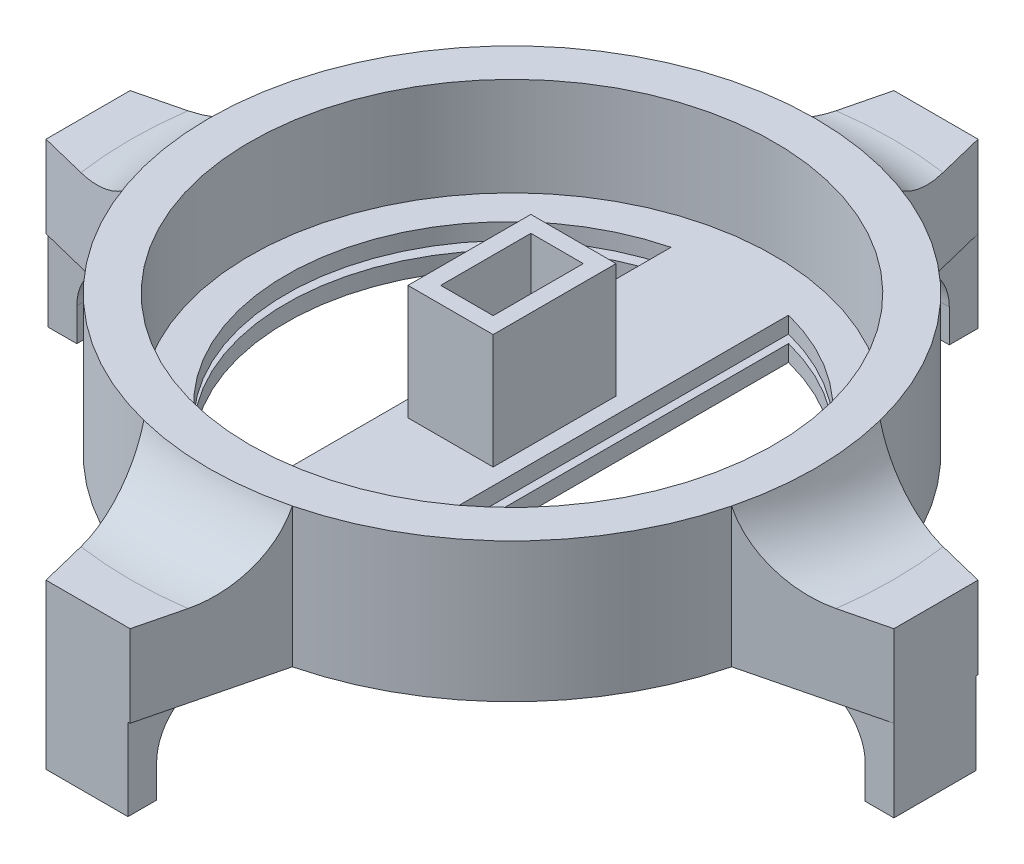
SolidWorks part; units mm, degrees
ref_plane "Front Plane" through (0, 0, 0) normal (0, 0, 1) x (1, 0, 0)
ref_plane "Top Plane" through (0, 0, 0) normal (0, 1, 0) x (1, 0, 0)
ref_plane "Right Plane" through (0, 0, 0) normal (1, 0, 0) x (0, 0, -1)
sketch "Sketch4" plane through (0, 0, 0) normal (0, 1, 0) x (1, 0, 0)
  line L0 (0, -46.7905) -> (24.3942, -46.7905) construction
  line L1 (0, -46.7905) -> (0, -24.9936) construction
  circle A0 centre (0, -46.7905) radius 17
  dimension "D1" = 34
extrude "Boss-Extrude3" add sketch "Sketch4" along normal blind 6 separate body
shell "Shell4" thickness 0.5 removed face at (0, 6, 63.7905) outward yes
ref_plane "Plane2" through (0, 0, 0) normal (0, 1, 0) x (1, 0, 0)
sketch "Sketch5" plane through (0, 0, 0) normal (0, 1, 0) x (1, 0, 0)
  line L0 (17, -46.7905) -> (-25.0436, -46.7905) construction
  line L1 (1.6, -44.0405) -> (-1.6, -44.0405)
  line L2 (1.6, -44.0405) -> (1.6, -49.5405)
  line L3 (1.6, -49.5405) -> (-1.6, -49.5405)
  line L4 (-1.6, -44.0405) -> (-1.6, -49.5405)
  line L5 (0, -29.7905) -> (0, -85.3723) construction
  circle A0 centre (0, -46.7905) radius 17 construction
  circle A1 centre (0, -46.7905) radius 17 construction
  dimension "D1" = 5.5
  dimension "D2" = 3.2
  dimension "D3" = 2.75
  dimension "D4" = 1.6
extrude "Boss-Extrude4" add sketch "Sketch5" along normal blind 8
shell "Shell5" thickness 1 removed face at (0, 8, 46.7905) outward yes
sketch "Sketch6" plane through (0, 0, 0) normal (0, 1, 0) x (1, 0, 0)
  line L1 (-2.5652, -72.6598) -> (2.5652, -72.6598)
  line L2 (2.5652, -72.6598) -> (4.5312, -64.727)
  line L3 (-2.5652, -72.6598) -> (-4.5312, -64.727)
  line L4 (-25.8693, -44.2252) -> (-17.9365, -42.2592)
  line L5 (-25.8693, -49.3557) -> (-17.9365, -51.3217)
  line L6 (-25.8693, -44.2252) -> (-25.8693, -49.3557)
  line L7 (2.5652, -20.9211) -> (4.5312, -28.854)
  line L8 (-2.5652, -20.9211) -> (-4.5312, -28.854)
  line L9 (2.5652, -20.9211) -> (-2.5652, -20.9211)
  line L10 (25.8693, -49.3557) -> (17.9365, -51.3217)
  line L11 (25.8693, -44.2252) -> (17.9365, -42.2592)
  line L12 (25.8693, -49.3557) -> (25.8693, -44.2252)
  circle A0 centre (0, -46.7905) radius 18.5 construction
  arc A1 (4.5312, -64.727) -> (-4.5312, -64.727) centre (0, -46.7905) cw
  arc A2 (-17.9365, -51.3217) -> (-17.9365, -42.2592) centre (0, -46.7905) cw
  arc A3 (-4.5312, -28.854) -> (4.5312, -28.854) centre (0, -46.7905) cw
  arc A4 (17.9365, -42.2592) -> (17.9365, -51.3217) centre (0, -46.7905) cw
  point P22 (0, -46.7905)
  dimension "D1" = 4
extrude "Boss-Extrude6" add sketch "Sketch6" against normal up to surface (1.5 mm away) and the other way blind 3.5 up to face at (0, -1.5, 65.2905)
sketch "Sketch7" plane through (0, -1.5, 0) normal (0, -1, 0) x (-1, 0, 0)
  line L0 (0, -20.9211) -> (0, -83.0743) construction
  line L1 (2.5652, -72.6598) -> (-2.4348, -72.6598)
  line L2 (2.5652, -72.6598) -> (2.5652, -70.9098)
  line L3 (2.5652, -70.9098) -> (-2.4348, -70.9098)
  line L4 (-2.4348, -72.6598) -> (-2.4348, -70.9098)
  line L5 (2.5652, -20.9211) -> (-2.5652, -20.9211) construction
  line L6 (25.8693, -46.7905) -> (-32.5376, -46.7905) construction
  line L7 (25.8693, -49.3557) -> (25.8693, -44.2252) construction
  line L8 (-25.8693, -49.3557) -> (-24.1193, -49.3557)
  line L9 (-25.8693, -49.3557) -> (-25.8693, -44.3557)
  line L10 (-25.8693, -44.3557) -> (-24.1193, -44.3557)
  line L11 (-24.1193, -49.3557) -> (-24.1193, -44.3557)
  line L12 (-2.5652, -20.9211) -> (-2.5652, -22.6711)
  line L13 (-2.5652, -20.9211) -> (2.4348, -20.9211)
  line L14 (2.4348, -20.9211) -> (2.4348, -22.6711)
  line L15 (-2.5652, -22.6711) -> (2.4348, -22.6711)
  line L16 (25.8693, -44.2252) -> (24.1193, -44.2252)
  line L17 (25.8693, -44.2252) -> (25.8693, -49.2252)
  line L18 (25.8693, -49.2252) -> (24.1193, -49.2252)
  line L19 (24.1193, -44.2252) -> (24.1193, -49.2252)
  point P14 (0, -46.7905)
  point P30 (0, -46.7905)
  dimension "D1" = 5
  dimension "D2" = 1.75
  dimension "D3" = 4
extrude "Boss-Extrude7" add sketch "Sketch7" along normal blind 5
fillet "Fillet1" radius 3 4 edges at (-0.0652, -1.5, 70.9098) (-24.1193, -1.5, 46.7252) (0.0652, -1.5, 22.6711) (24.1193, -1.5, 46.8557)
fillet "Fillet3" radius 5 4 edges at (0, 3.5, 65.2905) (-18.5, 3.5, 46.7905) (18.5, 3.5, 46.7905) (0, 3.5, 28.2905)
sketch "Sketch11" plane through (0, 1, 0) normal (0, 1, 0) x (1, 0, 0)
  line L0 (-3.5859, -59.9216) -> (-3.5859, -33.5012)
  line L1 (0, -44.0405) -> (0, -17.5543) construction
  line L2 (1.6, -44.0405) -> (-1.6, -44.0405) construction
  line L3 (3.5859, -59.9216) -> (3.5859, -33.5012)
  arc A0 (-3.5859, -59.9216) -> (-3.5859, -33.5012) centre (-0.2324, -46.7114) cw
  arc A1 (3.5859, -59.9216) -> (3.5859, -33.5012) centre (0.2324, -46.7114) ccw
extrude "Cut-Extrude1" cut sketch "Sketch11" against normal blind 5
sketch "Sketch13" plane through (0, -0.5, 0) normal (0, 1, 0) x (1, 0, 0)
  line L1 (-1.566, -49.504) -> (1.6, -49.504)
  line L2 (-1.566, -49.504) -> (-1.566, -44.0405)
  line L3 (-1.566, -44.0405) -> (1.6, -44.0405)
  line L4 (1.6, -49.504) -> (1.6, -44.0405)
  point P4 (1.238, -46.3907)
extrude "Cut-Extrude2" cut sketch "Sketch13" against normal blind 5
